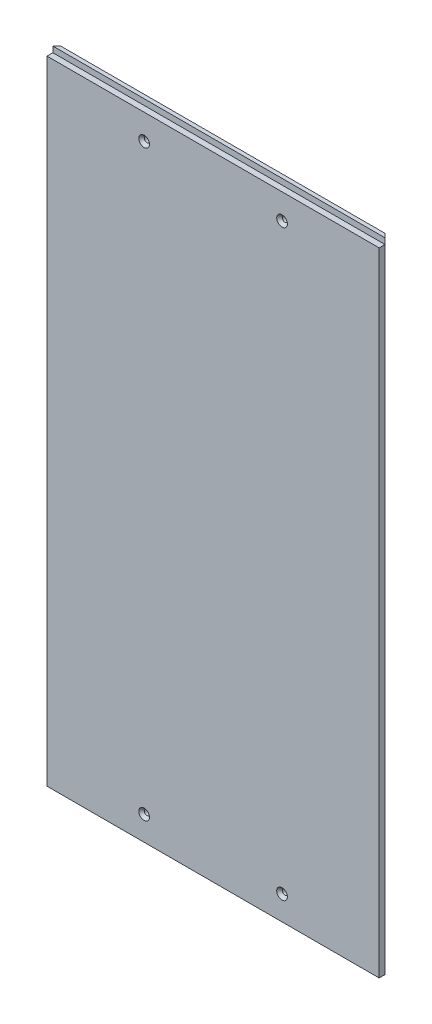
SolidWorks part; units mm, degrees
ref_plane "Front Plane" through (0, 0, 0) normal (0, 0, 1) x (1, 0, 0)
ref_plane "Top Plane" through (0, 0, 0) normal (0, 1, 0) x (1, 0, 0)
ref_plane "Right Plane" through (0, 0, 0) normal (1, 0, 0) x (0, 0, -1)
sketch "Sketch1" plane through (0, 0, 0) normal (0, 0, 1) x (1, 0, 0)
  line L1 (-171, -328.5) -> (171, -328.5)
  line L2 (-171, -328.5) -> (-171, 328.5)
  line L3 (-171, 328.5) -> (171, 328.5)
  line L4 (171, -328.5) -> (171, 328.5)
  line L5 (-171, -328.5) -> (171, 328.5) construction
  line L6 (-171, 328.5) -> (171, -328.5) construction
  point P0 (0, 0)
  dimension "ALTURA" = 657
  dimension "LARGURA" = 342
extrude "Boss-Extrude1" add sketch "Sketch1" along normal blind 12
sketch "Sketch2" plane through (-171, 0, 0) normal (-1, 0, 0) x (0, 0, 1)
  line L1 (12, 328.5) -> (6, 328.5)
  line L2 (12, 328.5) -> (12, 322.5)
  line L3 (12, 322.5) -> (6, 322.5)
  line L4 (6, 328.5) -> (6, 322.5)
  dimension "D1" = 6
  dimension "D2" = 6
extrude "Cut-Extrude1" cut sketch "Sketch2" against normal through all
chamfer "Chamfer1" distance 6 angle 45 2 edges at (171, 0, 0) (-171, 0, 0)
sketch "Sketch3" plane through (0, 0, 0) normal (0, 0, -1) x (-1, 0, 0)
  line L0 (-171, -328.5) -> (-171, 322.5) construction
  line L1 (165, -328.5) -> (-165, -328.5) construction
  line L2 (171, 322.5) -> (171, -328.5) construction
  line L3 (-165, 328.5) -> (165, 328.5) construction
  circle A0 centre (-71, -303.5) radius 2.6
  circle A1 centre (71, -303.5) radius 2.6
  circle A2 centre (71, 296.5) radius 2.6
  circle A3 centre (-71, 296.5) radius 2.6
  dimension "D1" = 5.2
  dimension "D2" = 100
  dimension "D3" = 25
  dimension "D4" = 100
  dimension "D5" = 32
extrude "Cut-Extrude2" cut sketch "Sketch3" against normal through all
chamfer "Chamfer2" distance 2.9 angle 45 4 edges at (-73.6, -303.5, 12) (68.4, -303.5, 12) (68.4, 296.5, 12) (-73.6, 296.5, 12)
sketch "Sketch4" plane through (0, 0, 0) normal (0, 0, -1) x (-1, 0, 0)
  line L0 (-165, 328.5) -> (165, 328.5) construction
  circle A0 centre (-91, 296.5) radius 6
  circle A1 centre (-51, 296.5) radius 6
  circle A2 centre (51, 296.5) radius 6
  circle A3 centre (91, 296.5) radius 6
  circle A5 centre (-71, 296.5) radius 2.6 construction
  circle A6 centre (71, 296.5) radius 2.6 construction
  dimension "D6" = 12
  dimension "D1" = 32
  dimension "D2" = 20
  dimension "D3" = 20
  dimension "D4" = 20
  dimension "D5" = 20
extrude "Cut-Extrude3" cut sketch "Sketch4" against normal blind 6
sketch "Sketch5" plane through (0, 0, 0) normal (0, 0, -1) x (-1, 0, 0)
  line L0 (-171, 280.5) -> (171, 280.5)
  line L1 (171, 280.5) -> (171, 328.5)
  line L2 (171, 328.5) -> (-171, 328.5)
  line L3 (-171, 328.5) -> (-171, 280.5)
  line L4 (-165, 328.5) -> (165, 328.5) construction
  line L5 (-171, -328.5) -> (-171, 322.5) construction
  line L6 (171, 322.5) -> (171, -328.5) construction
  dimension "D1" = 48
extrude "Cut-Extrude4" cut sketch "Sketch5" against normal blind 2
